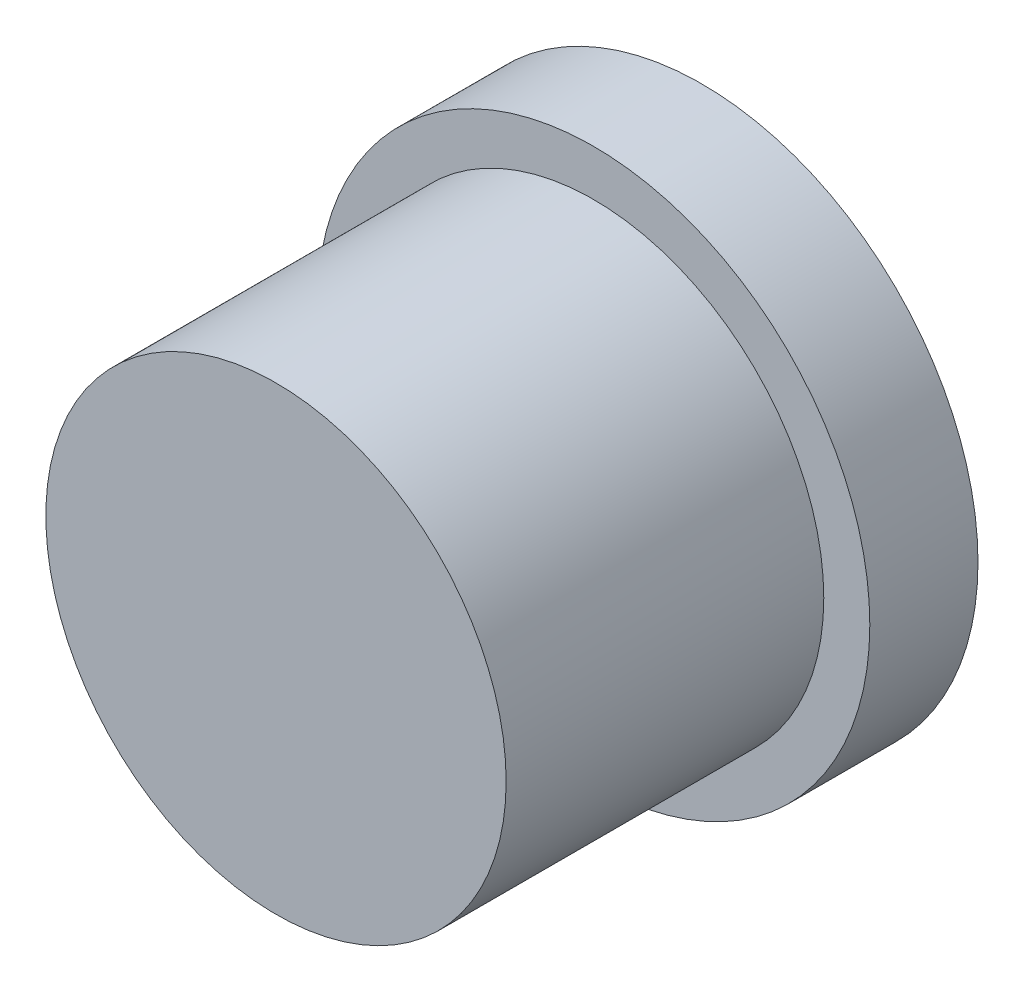
SolidWorks part; units mm, degrees
ref_plane "Front Plane" through (0, 0, 0) normal (0, 0, 1) x (1, 0, 0)
ref_plane "Top Plane" through (0, 0, 0) normal (0, 1, 0) x (1, 0, 0)
ref_plane "Right Plane" through (0, 0, 0) normal (1, 0, 0) x (0, 0, -1)
sketch "Sketch1" plane through (0, 0, 0) normal (0, 0, 1) x (1, 0, 0)
  circle A0 centre (0, 0) radius 24
  circle A1 centre (0, 0) radius 20
  circle A2 centre (0, 0) radius 17.5
  circle A4 centre (0, 12.5) radius 1
  circle A5 centre (12.5, 0) radius 1
  circle A6 centre (0, -12.5) radius 1
  circle A7 centre (-12.5, 0) radius 1
  point P17 (0, 0)
  dimension "D1" = 40
  dimension "D2" = 48
  dimension "D3" = 35
  dimension "D4" = 4
extrude "Boss-Extrude1" add sketch "Sketch1" along normal blind 9.4 contours A0 A1 | A1 A2 | A2 region at (-23.3212, 0, 0) region at (-19.4343, 0, 0) region at (0, 0, 0)
extrude "Boss-Extrude2" add sketch "Sketch1<4>" along normal blind 37 contours A6 | A5 | A7 | A4 | A2 A7 A6 A5 A4 | A1 A2 region at (-19.4343, 0, 0) region at (0, 0, 0) region at (0, 12.5, 0) region at (12.5, 0, 0) region at (0, -12.5, 0) region at (-12.5, 0, 0)
sketch "Sketch1<4>" plane through (0, 0, 0) normal (0, 0, 1) x (1, 0, 0) same geometry as "Sketch1"
extrude "Boss-Extrude3" add sketch "Sketch1<5>" against normal blind 4.5 contours A7 A6 A5 A4 | A2 A7 A4 A5 A6 region at (0, 0, 0)
sketch "Sketch1<5>" plane through (0, 0, 0) normal (0, 0, 1) x (1, 0, 0) same geometry as "Sketch1"
